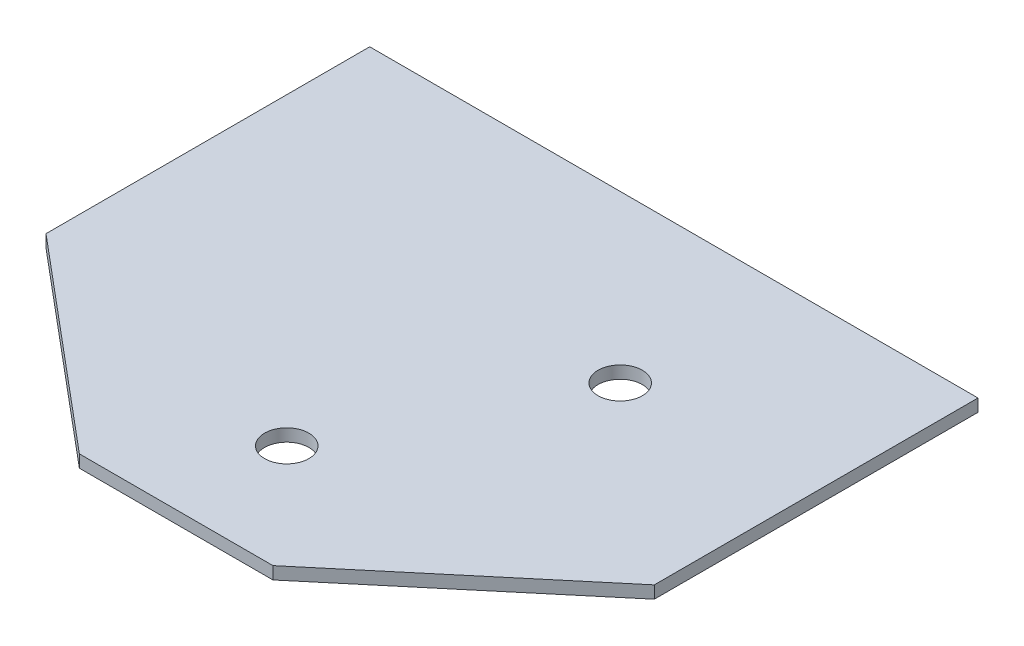
SolidWorks part; units mm, degrees
ref_plane "Front Plane" through (0, 0, 0) normal (0, 0, 1) x (1, 0, 0)
ref_plane "Top Plane" through (0, 0, 0) normal (0, 1, 0) x (1, 0, 0)
ref_plane "Right Plane" through (0, 0, 0) normal (1, 0, 0) x (0, 0, -1)
sketch "Sketch2" plane through (0, 0, 0) normal (0, 1, 0) x (1, 0, 0)
  line L3 (110, 90) -> (-110, 90)
  line L4 (110, 90) -> (110, -90)
  line L5 (110, -90) -> (-110, -90)
  line L6 (-110, 90) -> (-110, -90)
  line L7 (110, 90) -> (-110, -90) construction
  line L8 (110, -90) -> (-110, 90) construction
  point P0 (0, 0)
  dimension "D1" = 220
  dimension "D2" = 180
extrude "Boss-Extrude1" add sketch "Sketch2" along normal blind 4.5
chamfer "Chamfer1" distance 75 angle 40 2 edges at (-110, 2.25, 90) (110, 2.25, 90) first distance on face at (0, 2.25, 90)
sketch "Sketch3" plane through (0, 4.5, 0) normal (0, 1, 0) x (1, 0, 0)
  line L0 (0, 90) -> (0, -50) construction
  line L1 (110, 90) -> (-110, 90) construction
  line L2 (0, -50) -> (40.6, -50) construction
  line L3 (40.6, -50) -> (40.6, 30) construction
  circle A0 centre (0, -50) radius 8
  circle A1 centre (40.6, 30) radius 8
  dimension "D2" = 16
  dimension "D5" = 16
  dimension "D1" = 140
  dimension "D3" = 80
  dimension "D4" = 40.6
extrude "Cut-Extrude1" cut sketch "Sketch3" against normal through all
